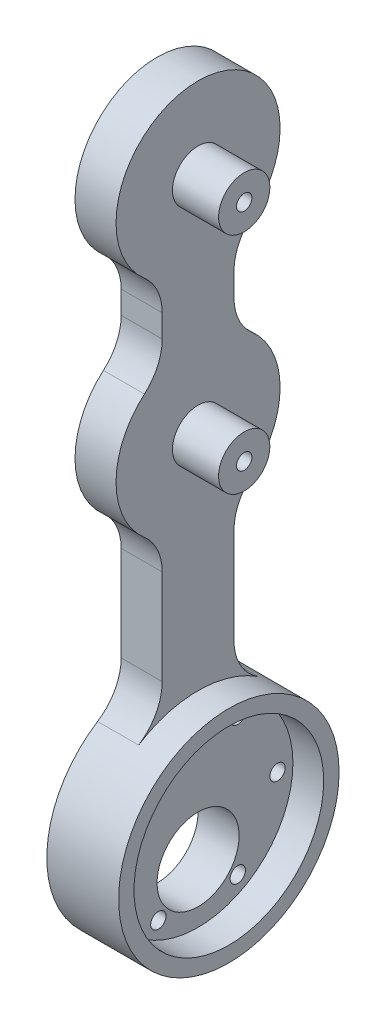
SolidWorks part; units mm, degrees
ref_plane "Front Plane" through (0, 0, 0) normal (0, 0, 1) x (1, 0, 0)
ref_plane "Top Plane" through (0, 0, 0) normal (0, 1, 0) x (1, 0, 0)
ref_plane "Right Plane" through (0, 0, 0) normal (1, 0, 0) x (0, 0, -1)
sketch "Sketch1" plane through (0, 0, 0) normal (1, 0, 0) x (0, 0, -1)
  line L0 (0, -108.491) -> (0, 108.491) construction
  line L1 (-70.7847, 0) -> (70.7847, 0) construction
  line L2 (-7, -14.3875) -> (-7, -29.3875)
  line L3 (-7, -58.1625) -> (-7, -88.1625)
  line L4 (7, -58.1625) -> (7, -88.1625)
  line L5 (7, -14.3875) -> (7, -29.3875)
  circle A0 centre (0, 0) radius 5
  arc A1 (7, -14.3875) -> (-7, -14.3875) centre (0, 0) ccw
  circle A2 centre (0, -43.775) radius 5
  arc A3 (-7, -29.3875) -> (-7, -58.1625) centre (0, -43.775) ccw
  arc A4 (-7, -88.1625) -> (7, -88.1625) centre (0, -108.491) ccw
  circle A5 centre (0, -108.491) radius 18.5
  arc A6 (7, -58.1625) -> (7, -29.3875) centre (0, -43.775) ccw
  point P4 (0, 0)
  point P8 (0, 0)
  dimension "D1" = 10
  dimension "D2" = 32
  dimension "D3" = 10
  dimension "D4" = 32
  dimension "D5" = 43
  dimension "D6" = 37
  dimension "D7" = 7
  dimension "D8" = 15
  dimension "D9" = 30
extrude "Boss-Extrude1" add sketch "Sketch1" along normal blind 4 and the other way blind 4 contours L3 A4 L4 A6 L5 A1 L2 A3
extrude "Boss-Extrude2" add sketch "Sketch1<3>" along normal blind 9 from surface contours A0 | A2 region at (0, 0, 0) region at (0, -43.775, 0) starting at face at (4, -48.9551, 0)
sketch "Sketch1<3>" plane through (0, 0, 0) normal (1, 0, 0) x (0, 0, -1) same geometry as "Sketch1"
sketch "Sketch2" plane through (-4, 0, 0) normal (-1, 0, 0) x (0, 0, 1)
  circle A0 centre (0, 0) radius 1.5
  arc A1 (-7, -29.3875) -> (-7, -58.1625) centre (0, -43.775) ccw construction
  arc A2 (-7, -29.3875) -> (-7, -58.1625) centre (0, -43.775) ccw construction
  circle A3 centre (0, -43.775) radius 1.5
  dimension "D1" = 3
  dimension "D2" = 3
extrude "Cut-Extrude1" cut sketch "Sketch2" against normal up to surface (17 mm away) up to face at (13, 0, -5)
sketch "Sketch3" plane through (4, 0, 0) normal (1, 0, 0) x (0, 0, -1)
  arc A0 (-7, -88.1625) -> (7, -88.1625) centre (0, -108.491) ccw construction
  arc A1 (-7, -88.1625) -> (7, -88.1625) centre (0, -108.491) ccw construction
  circle A2 centre (0, -108.491) radius 18.5
  circle A3 centre (0, -108.491) radius 21.5
  arc M8 (-7, -88.1625) -> (7, -88.1625) centre (0, -108.491) ccw
  dimension "D1" = 37
extrude "Boss-Extrude3" add sketch "Sketch3" along normal blind 6 contours A3 A2 M8 region at (4, -125.4995, 12.1319)
sketch "Sketch4" plane through (-4, 0, 0) normal (-1, 0, 0) x (0, 0, 1)
  line L0 (0, -86.991) -> (0, -129.991) construction
  line L1 (-21.5, -108.491) -> (21.5, -108.491) construction
  arc A0 (-7, -88.1625) -> (7, -88.1625) centre (0, -108.491) ccw construction
  arc A1 (-7, -88.1625) -> (7, -88.1625) centre (0, -108.491) ccw construction
  circle A2 centre (0, -115.491) radius 8
  circle A3 centre (15.4963, -108.491) radius 1.5
  circle A4 centre (7.7481, -95.0709) radius 1.5
  circle A5 centre (-7.7481, -95.0709) radius 1.5
  circle A6 centre (-15.4963, -108.491) radius 1.5
  circle A7 centre (-7.7481, -121.9112) radius 1.5
  circle A8 centre (7.7481, -121.9112) radius 1.5
  point P5 (0, -108.491)
  point P9 (0, -108.491)
  point P26 (0, -108.491)
  dimension "D2" = 16
  dimension "D4" = 3
  dimension "D1" = 7
  dimension "D3" = 15.4963
  dimension "D5" = 6
extrude "Cut-Extrude2" cut sketch "Sketch4" against normal up to surface (14 mm away) up to face at (10, -108.491, -18.5)
fillet "Fillet1" radius 10 8 edges at (0, -58.1625, 7) (0, -88.1625, 7) (0, -88.1625, -7) (0, -58.1625, -7) (0, -29.3875, -7) (0, -29.3875, 7) (0, -14.3875, 7) (0, -14.3875, -7)
